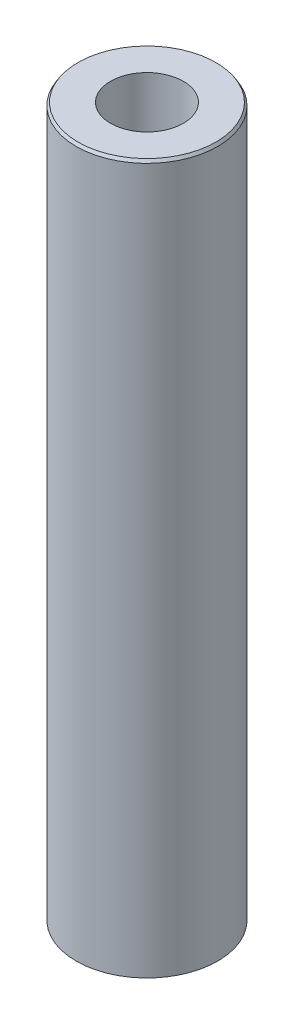
SolidWorks part; units mm, degrees
ref_plane "Front Plane" through (0, 0, 0) normal (0, 0, 1) x (1, 0, 0)
ref_plane "Top Plane" through (0, 0, 0) normal (0, 1, 0) x (1, 0, 0)
ref_plane "Right Plane" through (0, 0, 0) normal (1, 0, 0) x (0, 0, -1)
sketch "Sketch1" plane through (0, 0, 0) normal (0, 1, 0) x (1, 0, 0)
  circle A0 centre (0, 0) radius 27.5
  dimension "SHAFT_OD" = 55
extrude "Boss-Extrude1" add sketch "Sketch1" along normal blind 275.9165
sketch "Sketch2" plane through (0, 0, 0) normal (0, 1, 0) x (1, 0, 0)
  circle A0 centre (0, 0) radius 14.1528
  dimension "BORE_D" = 28.3057
extrude "Cut-Extrude1" cut sketch "Sketch2" along normal through all
chamfer "Chamfer1" distance 1.1118 angle 32.726 2 edges at (0, 275.9165, 27.5) (0, 0, 27.5) first distance on face at (0, 275.9165, 27.5) first distance on face at (0, 0, 14.1528)
